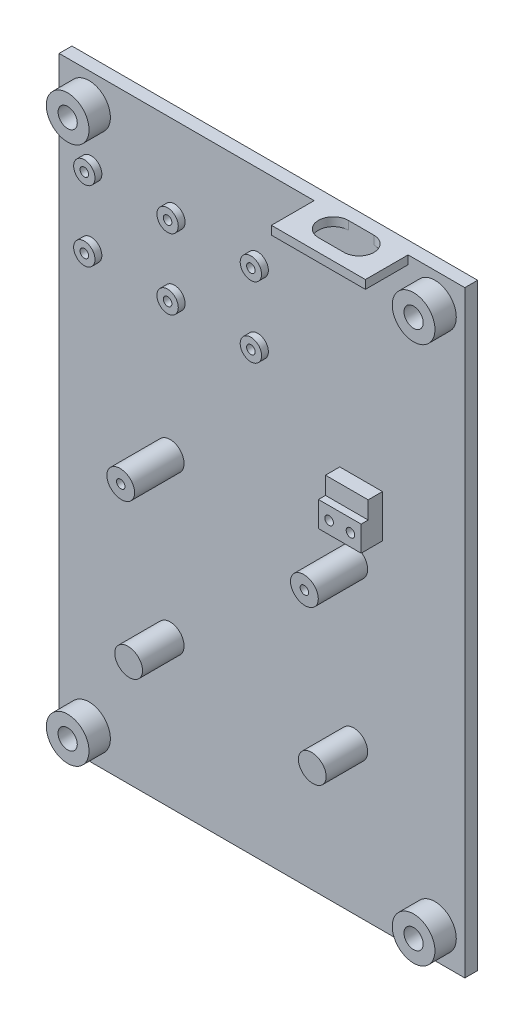
SolidWorks part; units mm, degrees
ref_plane "Front Plane" through (0, 0, 0) normal (0, 0, 1) x (1, 0, 0)
ref_plane "Top Plane" through (0, 0, 0) normal (0, 1, 0) x (1, 0, 0)
ref_plane "Right Plane" through (0, 0, 0) normal (1, 0, 0) x (0, 0, -1)
sketch "Sketch1" plane through (0, 0, 0) normal (0, 0, 1) x (1, 0, 0)
  line L1 (-36.192, 80.6962) -> (58.808, 80.6962)
  line L2 (-36.192, 80.6962) -> (-36.192, -59.3038)
  line L3 (-36.192, -59.3038) -> (58.808, -59.3038)
  line L4 (58.808, 80.6962) -> (58.808, -59.3038)
  dimension "D1" = 140
  dimension "D2" = 95
extrude "Boss-Extrude1" add sketch "Sketch1" along normal blind 3
sketch "Sketch2" plane through (0, 0, 0) normal (0, 0, 1) x (1, 0, 0)
  line L0 (-36.192, 80.6962) -> (-36.192, -59.3038) construction
  line L1 (58.808, 80.6962) -> (-36.192, 80.6962) construction
  line L2 (58.808, -59.3038) -> (58.808, 80.6962) construction
  line L3 (-36.192, -59.3038) -> (58.808, -59.3038) construction
  circle A0 centre (-29.192, 73.6962) radius 5
  circle A1 centre (51.808, 73.6962) radius 5
  circle A2 centre (51.808, -52.3038) radius 5
  circle A3 centre (-29.192, -52.3038) radius 5
  dimension "D1" = 10
  dimension "D2" = 10
  dimension "D3" = 10
  dimension "D4" = 10
  dimension "D5" = 7
  dimension "D6" = 7
  dimension "D7" = 7
  dimension "D8" = 7
extrude "Boss-Extrude2" add sketch "Sketch2" along normal blind 5 from surface starting at face at (11.308, 10.6962, 3)
sketch "Sketch3" plane through (0, 0, 0) normal (0, 0, 1) x (1, 0, 0)
  circle A0 centre (-29.192, 73.6962) radius 3.75
  circle A1 centre (51.808, 73.6962) radius 3.75
  circle A2 centre (51.808, -52.3038) radius 3.75
  circle A3 centre (-29.192, -52.3038) radius 3.75
  dimension "D1" = 7.5
  dimension "D2" = 7.5
  dimension "D3" = 7.5
  dimension "D4" = 7.5
extrude "Cut-Extrude1" cut sketch "Sketch3" along normal blind 4 from surface starting at face at (11.308, 10.6962, 0)
sketch "Sketch4" plane through (0, 0, 0) normal (0, 0, 1) x (1, 0, 0)
  circle A0 centre (51.808, 73.6962) radius 2.25
  circle A1 centre (-29.192, 73.6962) radius 2.25
  circle A2 centre (51.808, -52.3038) radius 2.25
  circle A3 centre (-29.192, -52.3038) radius 2.25
  dimension "D1" = 4.5
  dimension "D2" = 4.5
  dimension "D3" = 4.5
  dimension "D4" = 4.5
extrude "Cut-Extrude2" cut sketch "Sketch4" along normal through all
sketch "Sketch5" plane through (0, 0, 0) normal (0, 0, 1) x (1, 0, 0)
  line L0 (-31.192, 102.598) -> (-31.192, -58.293) construction
  line L1 (53.808, 83.1868) -> (53.808, -79.5781) construction
  line L2 (-36.192, 80.6962) -> (-36.192, -59.3038) construction
  line L4 (58.808, -59.3038) -> (58.808, 80.6962) construction
  line L5 (-90.8656, 30.6962) -> (111.5992, 30.6962) construction
  line L6 (-36.192, -59.3038) -> (58.808, -59.3038) construction
  circle A0 centre (-28.692, 44.6962) radius 2.5
  circle A1 centre (-28.692, 61.1962) radius 2.5
  circle A2 centre (-9.192, 61.1962) radius 2.5
  circle A3 centre (-9.192, 44.6962) radius 2.5
  circle A4 centre (10.308, 61.1962) radius 2.5
  circle A5 centre (10.308, 44.6962) radius 2.5
  dimension "D6" = 5
  dimension "D7" = 5
  dimension "D1" = 5
  dimension "D2" = 5
  dimension "D3" = 90
  dimension "D4" = 14
  dimension "D5" = 2.5
  dimension "D8" = 16.5
  dimension "D9" = 3
extrude "Boss-Extrude3" add sketch "Sketch5" along normal blind 1.6 from surface starting at face at (-24.192, -52.3038, 3)
sketch "Sketch6" plane through (0, 0, 0) normal (0, 0, 1) x (1, 0, 0)
  circle A0 centre (-28.692, 61.1962) radius 1
  circle A1 centre (-28.692, 44.6962) radius 1
  circle A2 centre (-9.192, 61.1962) radius 1
  circle A3 centre (10.308, 61.1962) radius 1
  circle A4 centre (-9.192, 44.6962) radius 1
  circle A5 centre (10.308, 44.6962) radius 1
  dimension "D1" = 2
  dimension "D2" = 2
  dimension "D3" = 2
  dimension "D4" = 2
  dimension "D5" = 2
  dimension "D6" = 2
extrude "Cut-Extrude3" cut sketch "Sketch6" against normal blind 4 from surface starting at face at (-26.192, 61.1962, 4.6)
sketch "Sketch7" plane through (0, 0, 0) normal (0, 0, 1) x (1, 0, 0)
  line L0 (44.808, 108.788) -> (44.808, -61.7468) construction
  line L1 (22.808, 106.9419) -> (22.808, -58.0546) construction
  line L2 (29.5234, 29.6962) -> (29.5234, 19.6962)
  line L3 (29.5234, 19.6962) -> (39.5234, 19.6962)
  line L4 (39.5234, 19.6962) -> (39.5234, 29.6962)
  line L5 (39.5234, 29.6962) -> (29.5234, 29.6962)
  line L6 (58.808, 80.6962) -> (-36.192, 80.6962) construction
  circle A2 centre (51.808, 73.6962) radius 5 construction
  dimension "D2" = 7
  dimension "D1" = 22
  dimension "D3" = 10
  dimension "D4" = 10
  dimension "D5" = 61
extrude "Boss-Extrude4" add sketch "Sketch7" along normal blind 3.35 from surface starting at face at (12.808, 61.1962, 3)
sketch "Sketch8" plane through (0, 0, 0) normal (0, 0, 1) x (1, 0, 0)
  line L0 (29.5234, 19.6962) -> (39.5234, 19.6962)
  line L1 (39.5234, 19.6962) -> (39.5234, 25.5962)
  line L2 (39.5234, 29.6962) -> (39.5234, 19.6962) construction
  line L3 (39.5234, 25.5962) -> (29.5234, 25.5962)
  line L4 (29.5234, 19.6962) -> (29.5234, 29.6962) construction
  line L5 (29.5234, 25.5962) -> (29.5234, 19.6962)
  line L6 (58.808, 80.6962) -> (-36.192, 80.6962) construction
  dimension "D1" = 55.1
extrude "Boss-Extrude5" add sketch "Sketch8" along normal blind 1.65 from surface starting at face at (34.5234, 24.6962, 6.35)
sketch "Sketch9" plane through (0, 0, 0) normal (0, 0, 1) x (1, 0, 0)
  line L0 (29.5234, 25.5962) -> (29.5234, 19.6962) construction
  line L1 (39.5234, 19.6962) -> (39.5234, 25.5962) construction
  line L2 (39.5234, 25.5962) -> (29.5234, 25.5962) construction
  circle A0 centre (32.0234, 22.5962) radius 1
  circle A1 centre (37.0234, 22.5962) radius 1
  dimension "D3" = 2
  dimension "D4" = 2
  dimension "D1" = 2.5
  dimension "D2" = 2.5
  dimension "D5" = 3
extrude "Cut-Extrude4" cut sketch "Sketch9" against normal blind 6 from surface starting at face at (34.5234, 22.6462, 8)
sketch "Sketch10" plane through (0, 0, 0) normal (0, 0, 1) x (1, 0, 0)
  line L0 (23.5234, 78.6962) -> (23.5234, 80.6962)
  line L1 (23.5234, 80.6962) -> (45.5234, 80.6962)
  line L2 (45.5234, 80.6962) -> (45.5234, 78.6962)
  line L3 (45.5234, 78.6962) -> (23.5234, 78.6962)
  line L6 (34.5234, 93.9111) -> (34.5234, 13.4391) construction
  line L7 (29.5234, 19.6962) -> (29.5234, 29.6962) construction
  line L8 (58.808, 80.6962) -> (-36.192, 80.6962) construction
  line L10 (58.808, -59.3038) -> (58.808, 80.6962) construction
  dimension "D1" = 22
  dimension "D2" = 2
  dimension "D3" = 5
  dimension "D4" = 11
  dimension "D5" = 24.2846
extrude "Boss-Extrude6" add sketch "Sketch10" along normal blind 10 from surface starting at face at (34.5234, 24.6962, 3)
sketch "Sketch12" plane through (0, 0, 0) normal (0, 1, 0) x (1, 0, 0)
  line L0 (31.5234, -3) -> (37.5234, -3)
  line L1 (31.5234, -10) -> (37.5234, -10)
  line L2 (23.5234, -13) -> (45.5234, -13) construction
  line L3 (45.5234, -3) -> (23.5234, -3) construction
  arc A0 (31.5234, -3) -> (31.5234, -10) centre (31.5234, -6.5) ccw
  arc A1 (37.5234, -10) -> (37.5234, -3) centre (37.5234, -6.5) ccw
  point P1 (34.5234, -13)
  point P11 (34.5234, -10)
  dimension "D1" = 7
  dimension "D2" = 7
  dimension "D3" = 6
extrude "Cut-Extrude5" cut sketch "Sketch12" against normal up to next from surface starting at face at (22.9157, 80.6962, 4.75)
sketch "Sketch14" plane through (0, 0, 0) normal (0, 0, 1) x (1, 0, 0)
  line L0 (-36.192, 80.6962) -> (-36.192, -59.3038) construction
  line L1 (-36.192, -59.3038) -> (58.808, -59.3038) construction
  line L2 (58.808, -59.3038) -> (58.808, 80.6962) construction
  circle A0 centre (-10.192, 12.1543) radius 3.25
  circle A1 centre (32.808, 12.1543) radius 3.25
  circle A2 centre (-10.192, -24.8457) radius 3.25
  circle A3 centre (32.808, -24.8457) radius 3.25
  dimension "D3" = 6.5
  dimension "D4" = 6.5
  dimension "D7" = 6.5
  dimension "D8" = 6.5
  dimension "D1" = 26
  dimension "D2" = 71.4581
  dimension "D5" = 26
  dimension "D6" = 34.4581
extrude "Boss-Extrude10" add sketch "Sketch14" along normal blind 20 from surface starting at face at (26.7849, 56.6962, 3)
sketch "Sketch13" plane through (0, 0, 0) normal (1, 0, 0) x (0, 0, -1)
  line L0 (-17.8463, 77.7375) -> (-10.1288, -76.7426) construction
  line L1 (-3, 80.6962) -> (-3, -59.3038) construction
  line L2 (-11, -47.8072) -> (-11, -64.9711) construction
  line L3 (-10.5891, -59.3038) -> (-23.7663, -59.3038) construction
  line L4 (-3, -59.3038) -> (0, -59.3038) construction
  line L5 (-14.9557, 19.8773) -> (-12.2744, -33.7944)
  line L6 (-12.2744, -33.7944) -> (-26.885, -34.5243)
  line L7 (-26.885, -34.5243) -> (-29.5664, 19.1474)
  line L8 (-29.5664, 19.1474) -> (-14.9557, 19.8773)
  point P10 (-11, -59.3038)
  point P16 (-11, -59.3038)
  dimension "D1" = 2.86
  dimension "D2" = 8
extrude "Cut-Extrude6" cut sketch "Sketch13" against normal through all both and the other way through all
sketch "Sketch15" plane through (0, 0, 0) normal (0, 0, 1) x (1, 0, 0)
  circle A0 centre (-10.192, 12.1543) radius 1
  circle A1 centre (32.808, 12.1543) radius 1
  dimension "D1" = 2
  dimension "D2" = 2
extrude "Cut-Extrude7" cut sketch "Sketch15" against normal blind 5 from surface starting at face at (-10.192, 8.9043, 14.4075)
